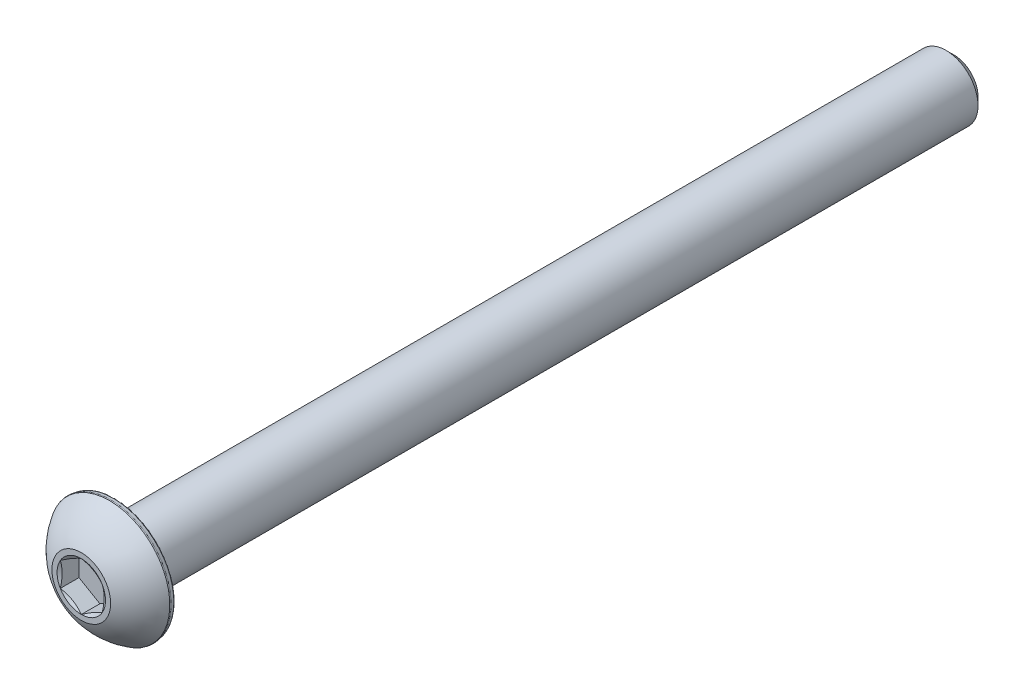
SolidWorks part; units mm, degrees
material "Alloy Steel"
ref_plane "Front Plane" through (0, 0, 0) normal (0, 0, 1) x (1, 0, 0)
ref_plane "Top Plane" through (0, 0, 0) normal (0, 1, 0) x (1, 0, 0)
ref_plane "Right Plane" through (0, 0, 0) normal (1, 0, 0) x (0, 0, -1)
sketch "Sketch1" plane through (0, 0, 0) normal (1, 0, 0) x (0, 0, -1)
  line L0 (-33.0327, 0) -> (33.0327, 0) construction
  line L1 (-33.0327, 0) -> (-33.0327, 4.5847)
  line L2 (-33.0327, 4.5847) -> (-30.4673, 4.5847)
  line L3 (-30.4673, 4.5847) -> (-30.4673, 2.413)
  line L4 (-30.4673, 2.413) -> (33.0327, 2.413)
  line L5 (33.0327, 2.413) -> (33.0327, 0)
  line L6 (33.0327, 0) -> (33.0327, -2.413) construction
  point P2 (0, 0)
  point P4 (32.239, 0)
  point P9 (31.8421, 2.413)
  point P10 (31.8421, -2.413)
  point P12 (-19.0055, 2.413)
  point P13 (23.8633, 2.413)
  point P14 (-21.2979, 2.413)
  point P15 (-31.6217, 0)
  dimension "Head Height" = 2.5654
  dimension "Head Diameter" = 9.1694
  dimension "Length" = 63.5
  dimension "Screw Size Decimal Equivalent" = 4.826
  dimension "Thread Pitch" = 0.7937
  dimension "D1" = 1.1906
  dimension "D2" = 1.411
  dimension "D3" = 9.1694
  dimension "D4" = 9.1694
  dimension "D5" = 11.4618
sketch "Sketch2" plane through (0, 0, 0) normal (0, 0, 1) x (1, 0, 0)
  line L0 (0, 2.413) -> (0, 0) construction
  line L1 (0, 1.8331) -> (-1.5875, 0.9165)
  line L2 (-1.5875, 0.9165) -> (-1.5875, -0.9165)
  line L3 (-1.5875, -0.9165) -> (0, -1.8331)
  line L4 (0, -1.8331) -> (1.5875, -0.9165)
  line L5 (1.5875, -0.9165) -> (1.5875, 0.9165)
  line L6 (1.5875, 0.9165) -> (0, 1.8331)
  circle A0 centre (0, 0) radius 1.5875 construction
  circle A1 centre (0, 0) radius 2.2225
  point P10 (0, 2.2225)
  dimension "D1" = 4.445
  dimension "Drive Size" = 3.175
sketch "Sketch3" plane through (0, 0, 0) normal (1, 0, 0) x (0, 0, -1)
  line L0 (-33.0327, 0) -> (-33.0327, 2.2225)
  line L1 (-33.0327, 0) -> (-33.0327, 4.5847) construction
  line L2 (-33.0327, 4.5847) -> (-30.4673, 4.5847) construction
  line L3 (-30.8521, 4.5847) -> (-30.4673, 4.5168)
  line L4 (-30.4673, 4.5847) -> (-30.4673, 2.413) construction
  line L5 (-30.4673, 4.5168) -> (-30.4673, 2.413)
  line L6 (-33.0327, 0) -> (33.0327, 0) construction
  line L7 (-33.0327, 0) -> (33.0327, 0)
  line L8 (33.0327, 0) -> (33.0327, 1.8177)
  line L9 (33.0327, 2.413) -> (33.0327, 0) construction
  line L10 (33.0327, 1.8177) -> (32.4374, 2.413)
  line L11 (-30.4673, 2.413) -> (33.0327, 2.413) construction
  line L12 (32.4374, 2.413) -> (-30.4673, 2.413)
  arc A0 (-33.0327, 2.2225) -> (-30.8521, 4.5847) centre (-28.2553, 0) cw
  dimension "D1" = 0.3848
  dimension "D2" = 10
  dimension "D3" = 45
  dimension "D4" = 0.5953
revolve "Revolve1" add sketch "Sketch3" angle 360 about L7
sketch "Sketch4" plane through (0, 0, 33.0327) normal (0, 0, 1) x (1, 0, 0)
  line L0 (-1.5875, -0.9165) -> (0, -1.8331) construction
  line L1 (-1.5875, 0.9165) -> (-1.5875, -0.9165) construction
  line L2 (0, 1.8331) -> (-1.5875, 0.9165) construction
  line L3 (1.5875, 0.9165) -> (0, 1.8331) construction
  line L4 (1.5875, -0.9165) -> (1.5875, 0.9165) construction
  line L5 (0, -1.8331) -> (1.5875, -0.9165) construction
  line L6 (-1.5875, -0.9165) -> (0, -1.8331)
  line L7 (-1.5875, 0.9165) -> (-1.5875, -0.9165)
  line L8 (0, 1.8331) -> (-1.5875, 0.9165)
  line L9 (1.5875, 0.9165) -> (0, 1.8331)
  line L10 (1.5875, -0.9165) -> (1.5875, 0.9165)
  line L11 (0, -1.8331) -> (1.5875, -0.9165)
extrude "Cut-Extrude1" cut sketch "Sketch4" against normal up to vertex (1.411 mm away) up to point (0, 0, 31.6217)
sketch "Sketch5" plane through (0, 0, 33.0327) normal (0, 0, 1) x (1, 0, 0)
  circle A0 centre (0, 0) radius 1.8331
extrude "Cut-Extrude2" cut sketch "Sketch5" against normal up to vertex (1.411 mm away) draft 60 up to point (0, 0, 31.6217)
fillet "Fillet1" radius 0.1283 2 edges at (4.5847, 0, 30.8521) (4.5168, 0, 30.4673)
split "Split1" [suppressed] bodies to split 106
sketch "Sketch6" [suppressed] plane through (0, 0, -33.0327) normal (0, 0, -1) x (-1, 0, 0)
  circle A0 centre (0, 0) radius 2.413 construction
  circle A1 centre (0, 0) radius 2.413
curve "Helix/Spiral1" [suppressed] pitch 0.7937 height 64.2938 turns 81
sketch "Sketch7" [suppressed] plane through (0, 0, 0) normal (1, 0, 0) x (0, 0, -1)
  line L0 (32.9831, 2.4989) -> (33.38, 1.8115) construction
  line L1 (33.38, 1.8115) -> (33.7768, 2.4989) construction
  line L2 (33.7768, 2.4989) -> (32.9831, 2.4989) construction
  line L3 (33.0079, 2.456) -> (33.752, 2.456)
  line L4 (33.752, 2.456) -> (33.4296, 1.8974)
  line L5 (33.4296, 1.8974) -> (33.3304, 1.8974)
  line L6 (33.3304, 1.8974) -> (33.0079, 2.456)
  line L7 (33.38, 1.8974) -> (33.38, 1.8115) construction
  line L8 (33.0327, 2.413) -> (33.7272, 2.413) construction
  line L9 (33.38, 2.4989) -> (33.38, 2.413) construction
  point P12 (33.38, 2.456)
  dimension "D1" = 0.7937
  dimension "D2" = 0.0992
sweep "Cut-Sweep1" [suppressed] cut profiles "Sketch7" path "Helix/Spiral1"
sketch "Sketch8" [suppressed] plane through (0, 0, 30.4673) normal (0, 0, -1) x (-1, 0, 0)
  circle A0 centre (0, 0) radius 2.4989
extrude "Boss-Extrude1" [suppressed] add sketch "Sketch8" along normal up to vertex draft 45
equation "\"D1@Sketch1\"=\"Thread Pitch@Sketch1\"*1.5"
equation "\"D2@Sketch1\"=0.55*\"Head Height@Sketch1\""
equation "\"D1@Sketch2\"=\"Drive Size@Sketch2\"*1.4"
equation "\"D1@Sketch3\"=0.15*\"Head Height@Sketch1\""
equation "\"D4@Sketch3\"=0.75*\"Thread Pitch@Sketch1\""
equation "\"D1@Fillet1\"=.05*\"Head Height@Sketch1\""
equation "\"D4@Helix/Spiral1\"=\"Thread Pitch@Sketch1\""
equation "\"D2@Sketch7\"=\"D1@Sketch7\"/8"
equation "\"D1@Sketch7\"=\"Thread Pitch@Sketch1\""
equation "\"D3@Sketch1\"=\"Head Diameter@Sketch1\""
equation "\"D4@Sketch1\"=\"Head Diameter@Sketch1\""
equation "\"D5@Sketch1\"=\"D3@Sketch1\"*1.25"
